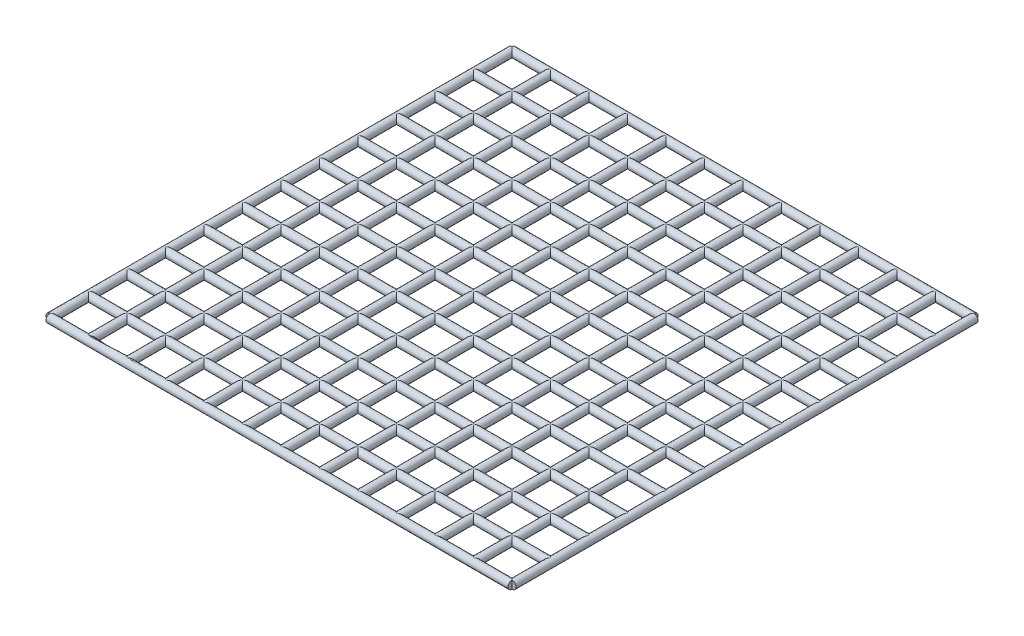
SolidWorks part; units mm, degrees
ref_plane "Front Plane" through (0, 0, 0) normal (0, 0, 1) x (1, 0, 0)
ref_plane "Top Plane" through (0, 0, 0) normal (0, 1, 0) x (1, 0, 0)
ref_plane "Right Plane" through (0, 0, 0) normal (1, 0, 0) x (0, 0, -1)
sketch "Sketch1" plane through (0, 0, 0) normal (0, 0, 1) x (1, 0, 0)
  circle A0 centre (0, 0) radius 1.3335
  dimension "D1" = 2.667
extrude "Boss-Extrude1" add sketch "Sketch1" against normal blind 152.4
sketch "Sketch2" plane through (0, 0, 0) normal (1, 0, 0) x (0, 0, -1)
  circle A0 centre (0, 0) radius 1.3335
extrude "Boss-Extrude2" add sketch "Sketch2" along normal blind 152.4
pattern_linear "LPattern1" count 13 spacing 12.7 along (1, 0, 0) of "Boss-Extrude1"
pattern_linear "LPattern2" count 13 spacing 12.7 along (0, 0, -1) of "Boss-Extrude2"
equation "\"D\"= 0.105in'Wire diameter"
equation "\"D1@Sketch1\"=\"D\""
equation "\"L\"= 6in'Mesh length"
equation "\"D1@Boss-Extrude1\"=\"L\""
equation "\"W\"= 6in'Mesh width"
equation "\"D1@Boss-Extrude2\"=\"W\""
equation "\"P\"= 0.5in'Wire pitch"
equation "\"D3@LPattern1\"=\"P\""
equation "\"D3@LPattern2\"=\"P\""
